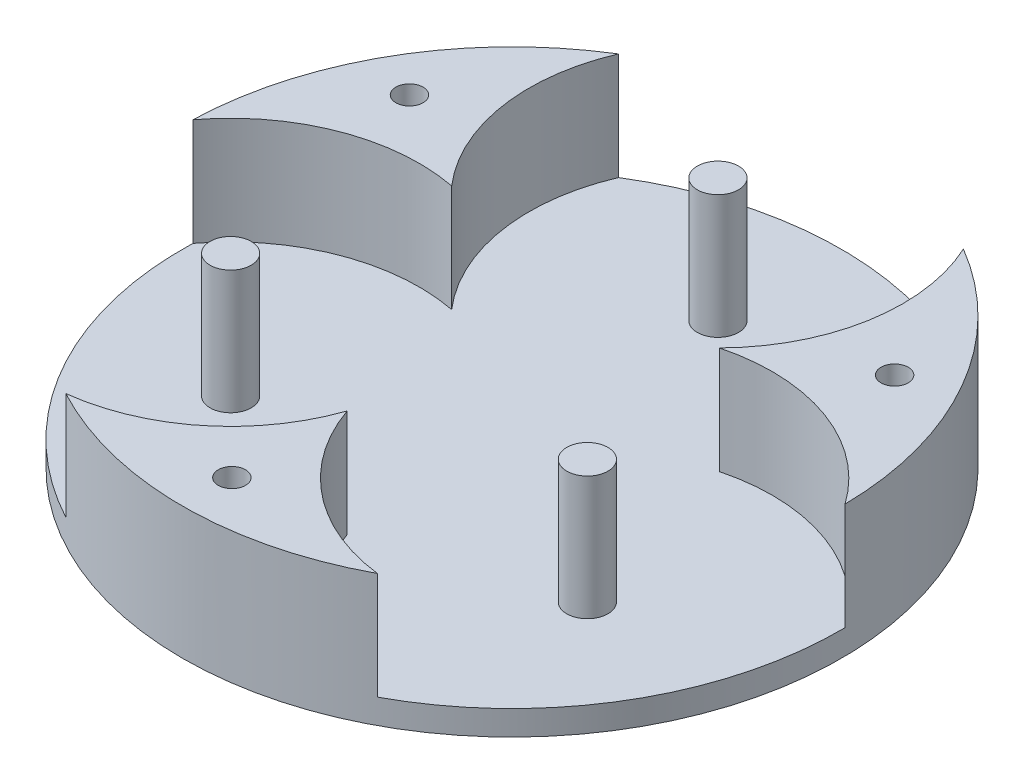
SolidWorks part; units mm, degrees
ref_plane "Front Plane" through (0, 0, 0) normal (0, 0, 1) x (1, 0, 0)
ref_plane "Top Plane" through (0, 0, 0) normal (0, 1, 0) x (1, 0, 0)
ref_plane "Right Plane" through (0, 0, 0) normal (1, 0, 0) x (0, 0, -1)
sketch "Sketch1" plane through (0, 0, 0) normal (0, 1, 0) x (1, 0, 0)
  line L0 (0, 0) -> (0, 25) construction
  line L1 (0, 0) -> (21.6506, -12.5) construction
  line L2 (0, 0) -> (-21.6506, -12.5) construction
  dimension "D1" = 25
  dimension "D2" = 120
  dimension "D3" = 120
sketch "Sketch3" plane through (0, 0, 0) normal (0, 1, 0) x (1, 0, 0)
  circle A0 centre (0, 0) radius 40
  dimension "D1" = 80
extrude "Boss-Extrude1" add sketch "Sketch3" along normal blind 3
sketch "Sketch4" plane through (0, 3, 0) normal (0, 1, 0) x (1, 0, 0)
  circle A0 centre (0, 25) radius 2.5
  circle A1 centre (21.6506, -12.5) radius 2.5
  circle A2 centre (-21.6506, -12.5) radius 2.5
  dimension "D1" = 5
extrude "Boss-Extrude2" add sketch "Sketch4" along normal blind 15
sketch "Sketch6" plane through (0, 3, 0) normal (0, 1, 0) x (1, 0, 0)
  line L0 (0, 0) -> (34.641, 20) construction
  line L1 (0, 0) -> (0, 25) construction
  line L2 (0, 0) -> (0, -40) construction
  line L3 (0, 0) -> (-34.641, 20) construction
  circle A2 centre (0, 0) radius 40 construction
  arc A3 (20.3723, 34.4234) -> (15.9546, 9.2114) centre (0, 25) cw
  arc A4 (15.9546, 9.2114) -> (39.9977, 0.4312) centre (21.6506, -12.5) cw
  arc A5 (39.9977, 0.4312) -> (20.3723, 34.4234) centre (0, 0) ccw
  arc A7 (0, -20) -> (-18.9092, -35.2483) centre (-21.6506, -12.5) cw
  arc A8 (0, -20) -> (18.9092, -35.2483) centre (21.6506, -12.5) ccw
  arc A9 (-18.9092, -35.2483) -> (18.9092, -35.2483) centre (0, 0) ccw
  arc A10 (-17.3205, 10) -> (-21.0713, 34) centre (0, 25) cw
  arc A11 (-17.3205, 10) -> (-39.9805, 1.2483) centre (-21.6506, -12.5) ccw
  arc A12 (-39.9805, 1.2483) -> (-21.0713, 34) centre (0, 0) cw
  dimension "D1" = 60
extrude "Boss-Extrude4" add sketch "Sketch6" along normal blind 13
sketch "Sketch7" plane through (0, 3, 0) normal (0, 1, 0) x (1, 0, 0)
  line L0 (0, 0) -> (34.641, 20) construction
  line L1 (0, 0) -> (-34.641, 20) construction
  circle A1 centre (0, -34) radius 1.65
  arc A2 (39.9977, 0.4312) -> (20.3723, 34.4234) centre (0, 0) ccw construction
  arc A3 (-21.0713, 34) -> (-39.9805, 1.2483) centre (0, 0) ccw construction
  circle A4 centre (-29.4449, 17) radius 1.65
  circle A5 centre (29.4449, 17) radius 1.65
  dimension "D1" = 3.3
extrude "Cut-Extrude4" cut sketch "Sketch7" against normal blind 13 and the other way blind 13
